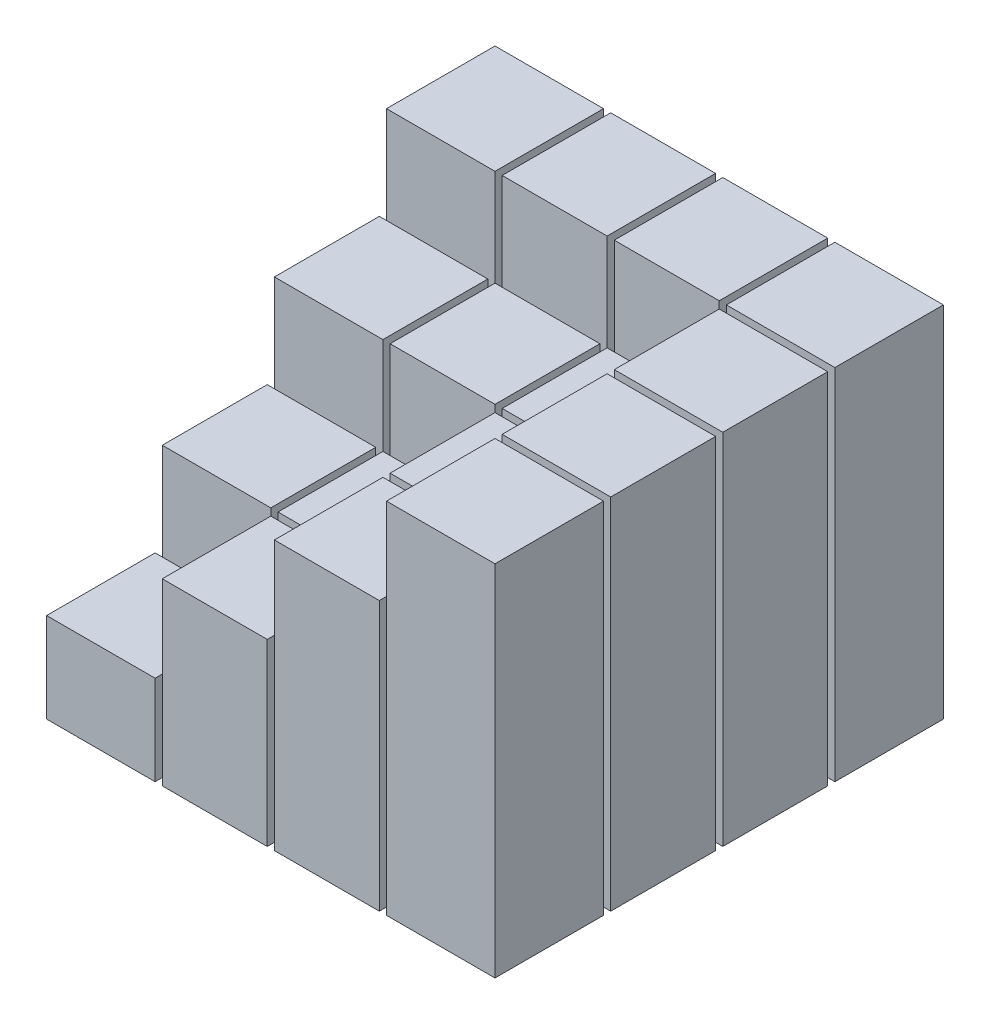
SolidWorks part; units mm, degrees
ref_plane "Front Plane" through (0, 0, 0) normal (0, 0, 1) x (1, 0, 0)
ref_plane "Top Plane" through (0, 0, 0) normal (0, 1, 0) x (1, 0, 0)
ref_plane "Right Plane" through (0, 0, 0) normal (1, 0, 0) x (0, 0, -1)
sketch "Sketch1" plane through (0, 0, 0) normal (0, 1, 0) x (1, 0, 0)
  line L1 (12.5, -12.5) -> (-12.5, -12.5)
  line L2 (12.5, -12.5) -> (12.5, 12.5)
  line L3 (12.5, 12.5) -> (-12.5, 12.5)
  line L4 (-12.5, -12.5) -> (-12.5, 12.5)
  line L5 (12.5, -12.5) -> (-12.5, 12.5) construction
  line L6 (12.5, 12.5) -> (-12.5, -12.5) construction
  point P0 (0, 0)
  dimension "D1" = 25
extrude "Boss-Extrude1" add sketch "Sketch1" along normal blind 5
sketch "Sketch2" plane through (0, 0, 0) normal (0, 1, 0) x (1, 0, 0)
  line L0 (-12.5, -12.5) -> (12.5, 12.5) construction
  line L1 (-12.5, 12.5) -> (12.5, 12.5)
  line L2 (-12.5, 12.5) -> (-12.5, -12.5)
  line L3 (-12.5, -12.5) -> (12.5, -12.5)
  line L4 (12.5, 12.5) -> (12.5, -12.5)
  line L6 (-12.5, -12.5) -> (-6.25, -12.5)
  line L7 (-12.5, -12.5) -> (-12.5, -6.25)
  line L8 (-12.5, -6.25) -> (-6.25, -6.25)
  line L9 (-6.25, -12.5) -> (-6.25, -6.25)
  line L10 (-12.5, -12.5) -> (0, -12.5)
  line L11 (-12.5, -12.5) -> (-12.5, 0)
  line L12 (-12.5, 0) -> (0, 0)
  line L13 (0, -12.5) -> (0, 0)
  line L14 (-12.5, -12.5) -> (6.25, -12.5)
  line L15 (-12.5, -12.5) -> (-12.5, 6.25)
  line L16 (-12.5, 6.25) -> (6.25, 6.25)
  line L17 (6.25, -12.5) -> (6.25, 6.25)
  point P6 (6.25, 6.25)
  point P7 (0, 0)
  point P8 (-6.25, -6.25)
  dimension "D1" = 6.25
  dimension "D2" = 6.25
extrude "Boss-Extrude2" add sketch "Sketch2" along normal blind 10 contours L8 L0 L12 L2 | L0 L9 L3 L13 | L12 L0 L16 L2 | L0 L13 L3 L17 | L16 L0 L1 L2 | L0 L17 L3 L4 region at (-7.6389, 0, 2.7778) region at (-2.7778, 0, 7.6389) region at (-4.5833, 0, -3.3333) region at (3.3333, 0, 4.5833) region at (-1.4881, 0, -9.5238) region at (9.5238, 0, 1.4881)
extrude "Boss-Extrude3" add sketch "Sketch2<3>" along normal blind 15 contours L12 L0 L16 L2 | L16 L0 L1 L2 | L0 L17 L3 L4 | L0 L13 L3 L17 region at (-4.5833, 0, -3.3333) region at (3.3333, 0, 4.5833) region at (-1.4881, 0, -9.5238) region at (9.5238, 0, 1.4881)
sketch "Sketch2<3>" plane through (0, 0, 0) normal (0, 1, 0) x (1, 0, 0) same geometry as "Sketch2"
extrude "Boss-Extrude4" add sketch "Sketch2<4>" along normal blind 20 contours L16 L0 L1 L2 | L0 L17 L3 L4 region at (-1.4881, 0, -9.5238) region at (9.5238, 0, 1.4881)
sketch "Sketch2<4>" plane through (0, 0, 0) normal (0, 1, 0) x (1, 0, 0) same geometry as "Sketch2"
sketch "Sketch3" plane through (0, 0, 0) normal (0, 1, 0) x (1, 0, 0)
  line L0 (-12.5, -6.25) -> (-6.45, -6.25) construction
  line L1 (12.5, 12.5) -> (12.5, -12.5) construction
  line L2 (-12.5, 0) -> (-6.45, 0) construction
  line L3 (-0.2, 6.25) -> (0, 6.25) construction
  line L4 (-6.25, -12.5) -> (-6.25, -6.45)
  line L5 (-12.5, 12.5) -> (12.5, 12.5) construction
  line L6 (0, -12.5) -> (0, -6.45) construction
  line L7 (6.25, -12.5) -> (6.25, -6.45) construction
  line L8 (-12.5, -0.2) -> (-6.45, -0.2)
  line L9 (-12.5, 6.05) -> (-6.45, 6.05)
  line L10 (-6.05, -12.5) -> (-6.05, -6.45)
  line L11 (0.2, -12.5) -> (0.2, -6.45)
  line L12 (6.45, -12.5) -> (6.45, -6.45)
  line L13 (-12.5, -6.45) -> (-6.45, -6.45)
  line L14 (-12.5, 0.2) -> (-6.45, 0.2)
  line L15 (-12.5, 6.45) -> (-6.45, 6.45)
  line L16 (-6.45, -12.5) -> (-6.45, -6.45)
  line L17 (-0.2, -12.5) -> (-0.2, -6.45)
  line L18 (6.05, -12.5) -> (6.05, -6.45)
  line L19 (-12.5, -6.05) -> (-6.45, -6.05)
  line L20 (-6.45, 6.25) -> (-6.45, 6.45) construction
  line L21 (-6.45, 6.45) -> (-6.45, 12.5)
  line L22 (-6.45, -12.5) -> (-6.45, 12.5) construction
  line L23 (-6.45, 6.45) -> (-6.25, 6.45) construction
  line L24 (-6.05, 6.45) -> (-0.2, 6.45)
  line L25 (-12.5, 6.45) -> (12.5, 6.45) construction
  line L26 (-6.25, 6.45) -> (-6.05, 6.45) construction
  line L27 (-6.05, 6.25) -> (-6.05, 6.45) construction
  line L28 (-6.05, 6.45) -> (-6.05, 12.5)
  line L29 (-6.05, -12.5) -> (-6.05, 12.5) construction
  line L30 (-6.25, 6.25) -> (-6.25, 6.45) construction
  line L31 (-6.25, 6.45) -> (-6.25, 12.5)
  line L32 (-6.25, -12.5) -> (-6.25, 12.5) construction
  line L33 (-12.5, 6.25) -> (-6.45, 6.25) construction
  line L34 (-12.5, 6.25) -> (12.5, 6.25) construction
  line L35 (-6.45, 6.05) -> (-6.45, 6.25) construction
  line L36 (-6.45, 6.25) -> (-6.25, 6.25) construction
  line L37 (-6.25, 6.25) -> (-6.05, 6.25) construction
  line L38 (-6.05, 6.05) -> (-6.05, 6.25) construction
  line L39 (-6.25, 6.05) -> (-6.25, 6.25) construction
  line L40 (-6.45, 6.05) -> (-6.25, 6.05) construction
  line L41 (-6.05, 6.05) -> (-0.2, 6.05)
  line L42 (-12.5, 6.05) -> (12.5, 6.05) construction
  line L43 (-6.25, 0.2) -> (-6.25, 6.05) construction
  line L44 (-6.25, 6.05) -> (-6.05, 6.05) construction
  line L45 (-0.2, 6.25) -> (-0.2, 6.45) construction
  line L46 (-0.2, 6.45) -> (-0.2, 12.5)
  line L47 (-0.2, -12.5) -> (-0.2, 12.5) construction
  line L48 (-0.2, 6.45) -> (0, 6.45) construction
  line L49 (0.2, 6.45) -> (6.05, 6.45)
  line L50 (0, 6.45) -> (0, 12.5) construction
  line L51 (0, -12.5) -> (0, 12.5) construction
  line L52 (0, 6.45) -> (0.2, 6.45) construction
  line L53 (0, 6.25) -> (0.2, 6.25) construction
  line L54 (6.05, 6.25) -> (6.25, 6.25) construction
  line L55 (0.2, 6.25) -> (0.2, 6.45) construction
  line L56 (0.2, 6.45) -> (0.2, 12.5)
  line L57 (0.2, -12.5) -> (0.2, 12.5) construction
  line L58 (0, 6.25) -> (0, 6.45) construction
  line L59 (-6.05, 6.25) -> (-0.2, 6.25) construction
  line L60 (-0.2, 6.05) -> (-0.2, 6.25) construction
  line L61 (0, 6.05) -> (0, 6.25) construction
  line L62 (0.2, 6.05) -> (0.2, 6.25) construction
  line L63 (0.2, 6.25) -> (6.05, 6.25) construction
  line L64 (-0.2, 6.05) -> (0, 6.05) construction
  line L65 (0.2, 6.05) -> (6.05, 6.05)
  line L66 (0, 0.2) -> (0, 6.05) construction
  line L67 (0, 6.05) -> (0.2, 6.05) construction
  line L68 (6.05, 6.25) -> (6.05, 6.45) construction
  line L69 (6.05, 6.45) -> (6.05, 12.5)
  line L70 (6.05, -12.5) -> (6.05, 12.5) construction
  line L71 (6.05, 6.45) -> (6.25, 6.45) construction
  line L72 (6.45, 6.45) -> (12.5, 6.45)
  line L73 (6.25, 6.45) -> (6.25, 12.5) construction
  line L74 (6.25, -12.5) -> (6.25, 12.5) construction
  line L75 (6.25, 6.45) -> (6.45, 6.45) construction
  line L76 (6.25, 6.25) -> (6.25, 6.45) construction
  line L77 (6.45, 6.25) -> (6.45, 6.45) construction
  line L78 (6.45, 6.45) -> (6.45, 12.5)
  line L79 (6.45, -12.5) -> (6.45, 12.5) construction
  line L80 (6.45, 6.25) -> (12.5, 6.25) construction
  line L81 (6.45, 6.05) -> (6.45, 6.25) construction
  line L82 (6.25, 6.25) -> (6.45, 6.25) construction
  line L83 (6.25, 6.05) -> (6.25, 6.25) construction
  line L84 (6.05, 6.05) -> (6.05, 6.25) construction
  line L85 (6.05, 6.05) -> (6.25, 6.05) construction
  line L86 (6.45, 6.05) -> (12.5, 6.05)
  line L87 (6.25, 0.2) -> (6.25, 6.05) construction
  line L88 (6.25, 6.05) -> (6.45, 6.05) construction
  line L89 (-6.45, 0) -> (-6.45, 0.2) construction
  line L90 (-6.45, 0.2) -> (-6.45, 6.05)
  line L91 (-6.45, 0.2) -> (-6.25, 0.2) construction
  line L92 (-6.05, 0.2) -> (-0.2, 0.2)
  line L93 (-12.5, 0.2) -> (12.5, 0.2) construction
  line L94 (-6.25, 0.2) -> (-6.05, 0.2) construction
  line L95 (-6.25, 0) -> (-6.25, 0.2) construction
  line L96 (-6.05, 0) -> (-6.05, 0.2) construction
  line L97 (-6.05, 0.2) -> (-6.05, 6.05)
  line L98 (-6.25, 0) -> (-6.05, 0) construction
  line L99 (-6.05, 0) -> (-0.2, 0) construction
  line L100 (-12.5, 0) -> (12.5, 0) construction
  line L101 (-6.05, -0.2) -> (-6.05, 0) construction
  line L102 (-6.25, -0.2) -> (-6.25, 0) construction
  line L103 (-6.45, 0) -> (-6.25, 0) construction
  line L104 (-6.45, -0.2) -> (-6.45, 0) construction
  line L105 (-6.45, -0.2) -> (-6.25, -0.2) construction
  line L106 (-6.05, -0.2) -> (-0.2, -0.2)
  line L107 (-12.5, -0.2) -> (12.5, -0.2) construction
  line L108 (-6.25, -0.2) -> (-6.05, -0.2) construction
  line L109 (-6.25, -6.05) -> (-6.25, -0.2) construction
  line L110 (-0.2, 0) -> (-0.2, 0.2) construction
  line L111 (-0.2, 0.2) -> (-0.2, 6.05)
  line L112 (-0.2, 0.2) -> (0, 0.2) construction
  line L113 (0.2, 0.2) -> (6.05, 0.2)
  line L114 (0, 0.2) -> (0.2, 0.2) construction
  line L115 (0.2, 0) -> (0.2, 0.2) construction
  line L116 (0.2, 0.2) -> (0.2, 6.05)
  line L117 (0, 0) -> (0, 0.2) construction
  line L118 (-0.2, 0) -> (0, 0) construction
  line L119 (0.2, 0) -> (6.05, 0) construction
  line L120 (-0.2, -0.2) -> (-0.2, 0) construction
  line L121 (0, 0) -> (0.2, 0) construction
  line L122 (0.2, -0.2) -> (0.2, 0) construction
  line L123 (0, -0.2) -> (0, 0) construction
  line L124 (-0.2, -0.2) -> (0, -0.2) construction
  line L125 (0.2, -0.2) -> (6.05, -0.2)
  line L126 (0, -6.05) -> (0, -0.2) construction
  line L127 (0, -0.2) -> (0.2, -0.2) construction
  line L128 (6.05, 0) -> (6.05, 0.2) construction
  line L129 (6.05, 0.2) -> (6.05, 6.05)
  line L130 (6.05, 0.2) -> (6.25, 0.2) construction
  line L131 (6.45, 0.2) -> (12.5, 0.2)
  line L132 (6.25, 0.2) -> (6.45, 0.2) construction
  line L133 (6.25, 0) -> (6.25, 0.2) construction
  line L134 (6.45, 0) -> (6.45, 0.2) construction
  line L135 (6.45, 0.2) -> (6.45, 6.05)
  line L136 (6.25, 0) -> (6.45, 0) construction
  line L137 (6.45, 0) -> (12.5, 0) construction
  line L138 (6.45, -0.2) -> (6.45, 0) construction
  line L139 (6.25, -0.2) -> (6.25, 0) construction
  line L140 (6.05, 0) -> (6.25, 0) construction
  line L141 (6.05, -0.2) -> (6.05, 0) construction
  line L142 (6.05, -0.2) -> (6.25, -0.2) construction
  line L143 (6.45, -0.2) -> (12.5, -0.2)
  line L144 (6.25, -6.05) -> (6.25, -0.2) construction
  line L145 (6.25, -0.2) -> (6.45, -0.2) construction
  line L146 (6.05, -6.25) -> (6.05, -6.05) construction
  line L147 (6.05, -6.05) -> (6.05, -0.2)
  line L148 (6.05, -6.05) -> (6.25, -6.05) construction
  line L149 (6.45, -6.05) -> (12.5, -6.05)
  line L150 (-12.5, -6.05) -> (12.5, -6.05) construction
  line L151 (6.25, -6.05) -> (6.45, -6.05) construction
  line L152 (6.25, -6.25) -> (6.25, -6.05) construction
  line L153 (6.45, -6.25) -> (6.45, -6.05) construction
  line L154 (6.45, -6.05) -> (6.45, -0.2)
  line L155 (6.25, -6.25) -> (6.45, -6.25) construction
  line L156 (6.45, -6.25) -> (12.5, -6.25) construction
  line L157 (-12.5, -6.25) -> (12.5, -6.25) construction
  line L158 (6.25, -6.45) -> (6.25, -6.25) construction
  line L159 (6.05, -6.45) -> (6.05, -6.25) construction
  line L160 (6.45, -6.45) -> (6.45, -6.25) construction
  line L161 (6.25, -6.45) -> (6.45, -6.45) construction
  line L162 (6.45, -6.45) -> (12.5, -6.45)
  line L163 (-12.5, -6.45) -> (12.5, -6.45) construction
  line L164 (6.05, -6.45) -> (6.25, -6.45) construction
  line L165 (-0.2, -6.25) -> (-0.2, -6.05) construction
  line L166 (-0.2, -6.05) -> (-0.2, -0.2)
  line L167 (0, -6.25) -> (0, -6.05) construction
  line L168 (0.2, -6.25) -> (0.2, -6.05) construction
  line L169 (0.2, -6.05) -> (0.2, -0.2)
  line L170 (0.2, -6.25) -> (6.05, -6.25) construction
  line L171 (6.05, -6.25) -> (6.25, -6.25) construction
  line L172 (0.2, -6.45) -> (0.2, -6.25) construction
  line L173 (0, -6.45) -> (0, -6.25) construction
  line L174 (-0.2, -6.45) -> (-0.2, -6.25) construction
  line L175 (-0.2, -6.05) -> (0, -6.05) construction
  line L176 (0.2, -6.05) -> (6.05, -6.05)
  line L177 (0, -6.05) -> (0.2, -6.05) construction
  line L178 (0, -6.45) -> (0.2, -6.45) construction
  line L179 (0.2, -6.45) -> (6.05, -6.45)
  line L180 (-0.2, -6.45) -> (0, -6.45) construction
  line L181 (-6.45, -6.25) -> (-6.45, -6.05) construction
  line L182 (-6.45, -6.05) -> (-6.45, -0.2)
  line L183 (-6.25, -6.25) -> (-6.25, -6.05) construction
  line L184 (-6.05, -6.25) -> (-6.05, -6.05) construction
  line L185 (-6.05, -6.05) -> (-6.05, -0.2)
  line L186 (-6.25, -6.05) -> (-6.05, -6.05) construction
  line L187 (-6.05, -6.05) -> (-0.2, -6.05)
  line L188 (-6.25, -6.25) -> (-6.05, -6.25) construction
  line L189 (-6.05, -6.25) -> (0.2, -6.25) construction
  line L190 (-6.25, -6.45) -> (-6.05, -6.45) construction
  line L191 (-6.05, -6.45) -> (-0.2, -6.45)
  line L192 (-6.05, -6.45) -> (-6.05, -6.25) construction
  line L193 (-6.25, -6.45) -> (-6.25, -6.25) construction
  line L194 (-6.45, -6.45) -> (-6.45, -6.25) construction
  line L195 (-6.45, -6.45) -> (-6.25, -6.45) construction
  line L196 (-6.45, -6.05) -> (-6.25, -6.05) construction
  line L197 (-6.45, -6.25) -> (-6.25, -6.25) construction
  arc A0 (-12.5, -0.2) -> (-12.5, 0.2) centre (-12.5, 0) cw
  arc A1 (12.5, -0.2) -> (12.5, 0.2) centre (12.5, 0) ccw
  arc A2 (-12.5, 6.05) -> (-12.5, 6.45) centre (-12.5, 6.25) cw
  arc A3 (12.5, 6.05) -> (12.5, 6.45) centre (12.5, 6.25) ccw
  arc A4 (-6.05, -12.5) -> (-6.45, -12.5) centre (-6.25, -12.5) cw
  arc A5 (-6.05, 12.5) -> (-6.45, 12.5) centre (-6.25, 12.5) ccw
  arc A6 (0.2, -12.5) -> (-0.2, -12.5) centre (0, -12.5) cw
  arc A7 (0.2, 12.5) -> (-0.2, 12.5) centre (0, 12.5) ccw
  arc A8 (6.45, -12.5) -> (6.05, -12.5) centre (6.25, -12.5) cw
  arc A9 (6.45, 12.5) -> (6.05, 12.5) centre (6.25, 12.5) ccw
  arc A10 (-12.5, -6.45) -> (-12.5, -6.05) centre (-12.5, -6.25) cw
  arc A11 (12.5, -6.45) -> (12.5, -6.05) centre (12.5, -6.25) ccw
  dimension "D1" = 0.2
  dimension "D2" = 0.2
extrude "Cut-Extrude1" cut sketch "Sketch3" along normal through all contours L162 A11 L149 L154 L143 A1 L131 L135 L86 A3 L72 L78 A9 L69 L49 L56 A7 L46 L24 L28 A5 L21 L15 A2 L9 L90 L14 A0 L8 L182 L19 A10 L13 L16 A4 L10 L191 L17 A6 L11 L179 L18 A8 L12 region at (0, 0, 0)
sketch "Sketch4" plane through (0, 0, 0) normal (0, 1, 0) x (1, 0, 0)
  line L0 (-12.5, -12.5) -> (-6.45, -6.45) construction
  circle A0 centre (-9.475, -9.475) radius 0.8
  circle A1 centre (-3.225, -9.475) radius 0.8
  circle A2 centre (3.025, -9.475) radius 0.8
  circle A3 centre (9.275, -9.475) radius 0.8
  circle A4 centre (-3.225, -3.225) radius 0.8
  circle A5 centre (3.025, -3.225) radius 0.8
  circle A6 centre (9.275, -3.225) radius 0.8
  circle A7 centre (-3.225, 3.025) radius 0.8
  circle A8 centre (3.025, 3.025) radius 0.8
  circle A9 centre (9.275, 3.025) radius 0.8
  circle A10 centre (-3.225, 9.275) radius 0.8
  circle A11 centre (3.025, 9.275) radius 0.8
  circle A12 centre (9.275, 9.275) radius 0.8
  circle A13 centre (-9.475, -3.225) radius 0.8
  circle A14 centre (-9.475, 3.025) radius 0.8
  circle A15 centre (-9.475, 9.275) radius 0.8
  dimension "D1" = 1.6
  dimension "D2" = 4
  dimension "D3" = 4
extrude "Cut-Extrude2" cut sketch "Sketch4" along normal blind 4
